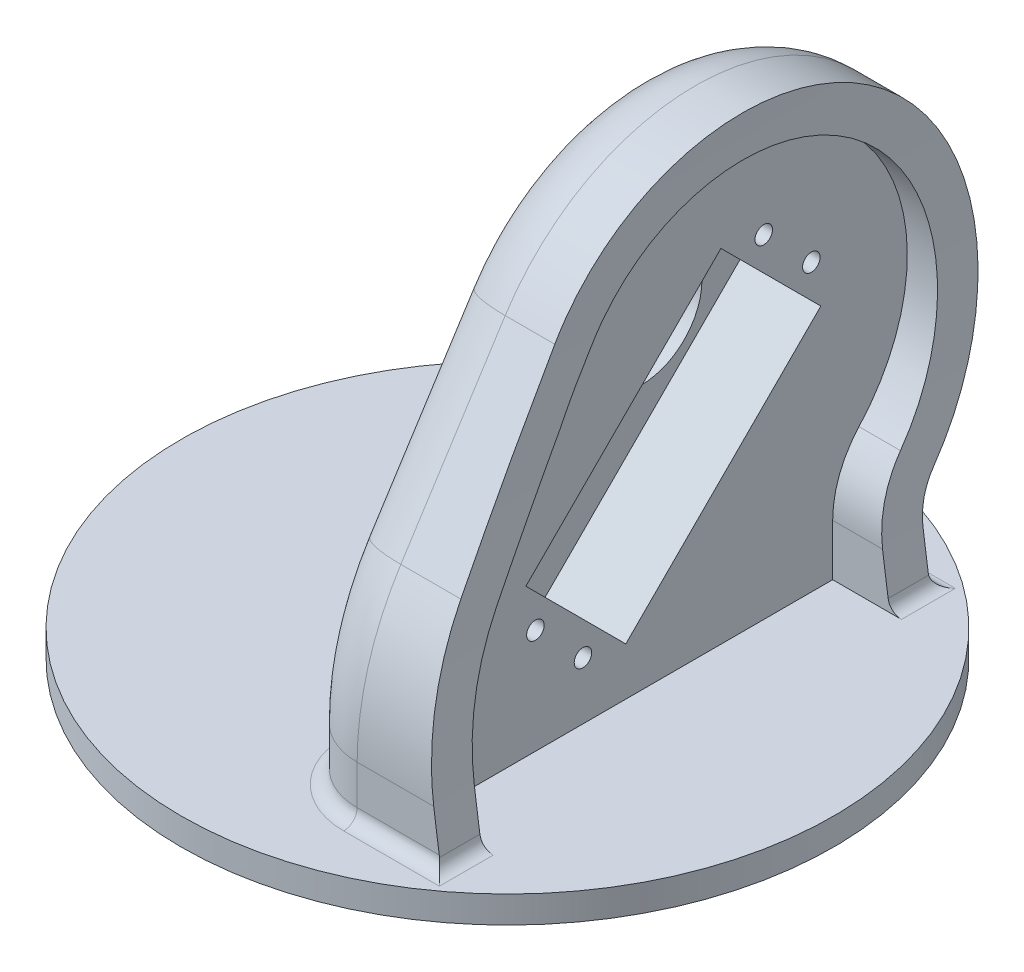
SolidWorks part; units mm, degrees
ref_plane "Front Plane" through (0, 0, 0) normal (0, 0, 1) x (1, 0, 0)
ref_plane "Top Plane" through (0, 0, 0) normal (0, 1, 0) x (1, 0, 0)
ref_plane "Right Plane" through (0, 0, 0) normal (1, 0, 0) x (0, 0, -1)
sketch "Sketch1" plane through (0, 0, 0) normal (0, 1, 0) x (1, 0, 0)
  line L0 (0, -7.25) -> (0, 7.25)
  circle A0 centre (0, 0) radius 48.5
  circle A1 centre (0, 7.25) radius 1.5
  circle A2 centre (0, -7.25) radius 1.5
  point P5 (0, 0)
  dimension "D2" = 97
  dimension "D3" = 3
  dimension "D1" = 14.5
extrude "Boss-Extrude1" add sketch "Sketch1" along normal blind 4 contours A0 A2 A1 region at (-47.1282, 0, 0)
sketch "Sketch2" plane through (0, 0, 0) normal (0, -1, 0) x (1, 0, 0)
  circle A0 centre (0, 0) radius 3.75
  dimension "D1" = 7.5
extrude "Cut-Extrude1" cut sketch "Sketch2" against normal blind 1.5
sketch "Sketch3" plane through (0, 0, 0) normal (1, 0, 0) x (0, 0, -1)
  line L0 (30.34, 4) -> (-30.34, 4)
  line L1 (48.5, 4) -> (-48.5, 4) construction
  line L2 (30.34, 4) -> (30.34, 11.64)
  line L3 (-30.34, 4) -> (-30.34, 11.86)
  line L4 (-9.2781, 55.1041) -> (-24.7927, 30.8361)
  arc A0 (30.34, 11.64) -> (34.2527, 21.7431) centre (45.34, 11.64) cw
  arc A1 (34.2527, 21.7431) -> (-9.2781, 55.1041) centre (13.91, 40.28) ccw
  arc A2 (-30.34, 11.86) -> (-24.7927, 30.8361) centre (4.89, 11.86) cw
  circle A3 centre (13.91, 40.28) radius 9
  point P5 (0, 4)
  dimension "D3" = 15
  dimension "D5" = 35.23
  dimension "D6" = 18
  dimension "D1" = 60.68
  dimension "D2" = 7.64
  dimension "D4" = 7.86
  dimension "D7" = 13.91
  dimension "D8" = 40.28
extrude "Boss-Extrude2" add sketch "Sketch3" along normal blind 14 from offset 4
sketch "Sketch4" plane through (0, 0, 0) normal (1, 0, 0) x (0, 0, -1)
  line L0 (-0.41, 11.11) -> (28.5814, 40.1014)
  line L1 (-0.41, 11.11) -> (-15.2592, 25.9592)
  line L2 (28.5814, 40.1014) -> (13.7321, 54.9506)
  line L3 (-15.2592, 25.9592) -> (13.7321, 54.9506)
  line L4 (-30.34, 4) -> (30.34, 4) construction
  line L5 (-0.7636, 40.4549) -> (14.0857, 25.6057) construction
  line L6 (6.6611, 33.0303) -> (23.6316, 50.0009) construction
  line L7 (20.0961, 53.5364) -> (27.1672, 46.4653)
  circle A0 centre (20.0961, 53.5364) radius 1.3
  circle A1 centre (27.1672, 46.4653) radius 1.3
  circle A2 centre (-6.774, 12.5242) radius 1.3
  circle A3 centre (-13.845, 19.5953) radius 1.3
  point P14 (23.6316, 50.0009)
  dimension "D8" = 2.6
  dimension "D1" = 0.41
  dimension "D2" = 11.11
  dimension "D3" = 21
  dimension "D4" = 41
  dimension "D5" = 45
  dimension "D6" = 3.5
  dimension "D7" = 10
extrude "Cut-Extrude3" cut sketch "Sketch4" along normal through all from offset 6 contours L3 L1 L0 L2 | A3 | A2 | A0 | A1 region at (0, 33.0303, -6.6611)
sketch "Sketch5" plane through (18, 0, 0) normal (1, 0, 0) x (0, 0, -1)
  line L0 (33.34, 4) -> (33.34, 11.64) construction
  line L1 (-11.8057, 56.7201) -> (-27.3203, 32.452) construction
  line L2 (-33.34, 11.86) -> (-33.34, 4) construction
  line L3 (36.34, 4) -> (36.34, 11.64)
  line L4 (-30.34, 11.86) -> (-30.34, 4)
  line L5 (-30.34, 4) -> (30.34, 4)
  line L6 (30.34, 4) -> (30.34, 11.64)
  line L7 (-9.2781, 55.1041) -> (-24.7927, 30.8361)
  line L9 (-30.34, 4) -> (30.34, 4)
  line L10 (30.34, 4) -> (30.34, 11.64)
  line L12 (-14.3333, 58.336) -> (-29.8479, 34.0679)
  line L13 (-36.34, 11.86) -> (-36.34, 4)
  line L14 (-9.2781, 55.1041) -> (-24.7927, 30.8361) construction
  line L15 (-30.34, 11.86) -> (-30.34, 4) construction
  line L16 (-36.34, 4) -> (-27.34, 4)
  line L17 (36.34, 4) -> (30.34, 4)
  arc A0 (36.4702, 19.7225) -> (33.34, 11.64) centre (45.34, 11.64) ccw construction
  arc A1 (36.4702, 19.7225) -> (-11.8057, 56.7201) centre (13.91, 40.28) ccw construction
  arc A2 (-27.3203, 32.452) -> (-33.34, 11.86) centre (4.89, 11.86) ccw construction
  arc A3 (34.2527, 21.7431) -> (30.34, 11.64) centre (45.34, 11.64) ccw
  arc A4 (34.2527, 21.7431) -> (-9.2781, 55.1041) centre (13.91, 40.28) ccw
  arc A5 (-24.7927, 30.8361) -> (-30.34, 11.86) centre (4.89, 11.86) ccw
  arc A6 (34.2527, 21.7431) -> (30.34, 11.64) centre (45.34, 11.64) ccw
  arc A7 (34.2527, 21.7431) -> (-9.2781, 55.1041) centre (13.91, 40.28) ccw
  arc A9 (38.6876, 17.7018) -> (36.34, 11.64) centre (45.34, 11.64) ccw
  arc A10 (38.6876, 17.7018) -> (-14.3333, 58.336) centre (13.91, 40.28) ccw
  arc A11 (-29.8479, 34.0679) -> (-36.34, 11.86) centre (4.89, 11.86) ccw
  arc A12 (-9.2781, 55.1041) -> (-27.34, 4) centre (72.447, -2.5241) ccw
  arc A13 (-24.7927, 30.8361) -> (-30.34, 11.86) centre (4.89, 11.86) ccw construction
  line M17 (-30.34, 11.86) -> (-30.34, 4)
  line M19 (30.34, 4) -> (30.34, 11.64)
  arc M20 (30.34, 11.64) -> (34.2527, 21.7431) centre (45.34, 11.64) cw
  arc M21 (34.2527, 21.7431) -> (-9.2781, 55.1041) centre (13.91, 40.28) ccw
  line M22 (-9.2781, 55.1041) -> (-24.7927, 30.8361)
  arc M23 (-24.7927, 30.8361) -> (-30.34, 11.86) centre (4.89, 11.86) ccw
  dimension "D5" = 100
  dimension "D4" = 3
  dimension "D1" = 0
  dimension "D2" = 3
  dimension "D3" = 3
extrude "Boss-Extrude3" add sketch "Sketch5" along normal blind 9 and the other way up to surface (14 mm away) contours A12 L17 L3 A9 A10 L12 A11 L13 L16 M21 M20 M19 M17 M23 M22 region at (18, 5.0904, -33.34) other way up to face at (4, 23.3781, -2.2919)
sketch "Sketch6" plane through (0, 0, 0) normal (0, 0, 1) x (1, 0, 0)
  line L0 (27, 73.8017) -> (21, 73.8017)
  line L1 (48.5, 4) -> (-48.5, 4) construction
  line L2 (26.5, 4) -> (27, 4)
  line L3 (27, 4) -> (27, 73.8017)
  arc A0 (21, 73.8017) -> (26.5, 4) centre (520.9817, 78.08) ccw
  dimension "D3" = 500
  dimension "D1" = 6
  dimension "D2" = 0.5
extrude "Cut-Extrude4" cut sketch "Sketch6" against normal through all both and the other way through all
fillet "Fillet1" radius 10 6 edges at (4, 7.82, -36.34) (4, 14.8903, -36.9474) (4, 7.93, 36.34) (4, 23.4287, 34.6837) (4, 46.2019, 22.0906) (4, 66.8867, -34.3008)
fillet "Fillet2" radius 2 7 edges at (20.25, 4, 36.34) (6.9289, 4, 33.4111) (20.25, 4, -36.34) (6.9289, 4, -33.4111) (26.5, 4, -33.34) (26.5, 4, 33.34) (4, 4, 0)
